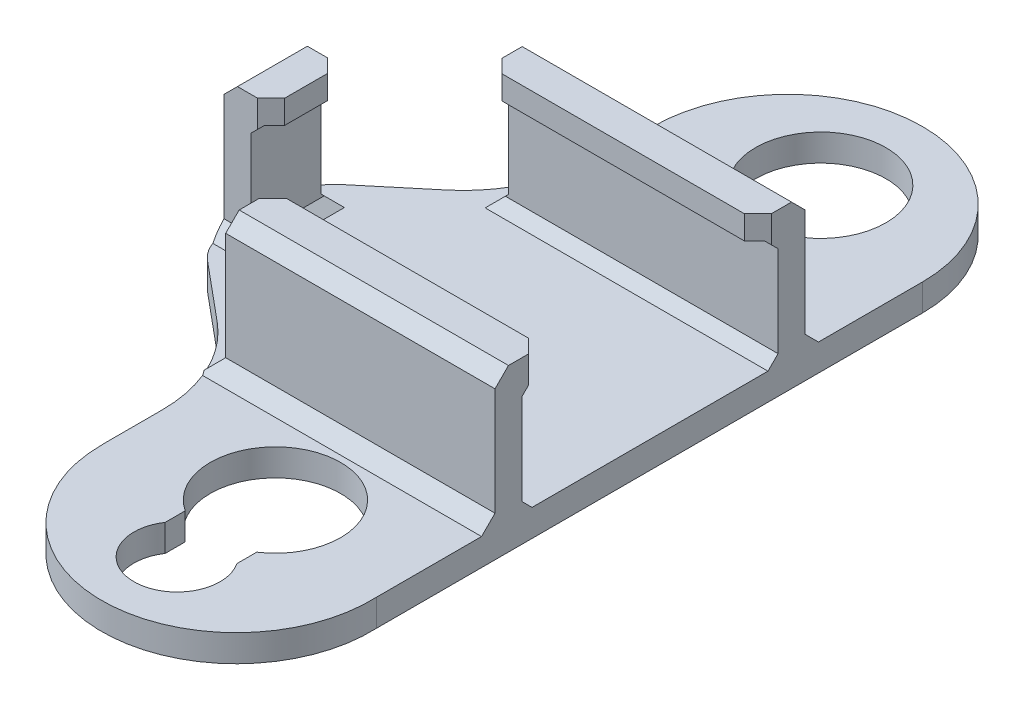
SolidWorks part; units mm, degrees
ref_plane "Front Plane" through (0, 0, 0) normal (0, 0, 1) x (1, 0, 0)
ref_plane "Top Plane" through (0, 0, 0) normal (0, 1, 0) x (1, 0, 0)
ref_plane "Right Plane" through (0, 0, 0) normal (1, 0, 0) x (0, 0, -1)
sketch "Sketch1" plane through (0, 0, 0) normal (0, 1, 0) x (1, 0, 0)
  line L0 (1.6716, 17.1781) -> (1.6716, -5.8219) construction
  line L1 (-8.3284, -14.595) -> (-8.3197, -15.0114)
  line L2 (1.6716, -19.4069) -> (1.6716, -12.0976)
  line L3 (11.6716, -5.8219) -> (-8.3284, -5.8219) construction
  line L4 (11.6716, 17.1781) -> (11.6716, -5.8219)
  line L5 (-17.3284, 8.273) -> (-17.3284, 3.0832)
  line L6 (-11.9265, 14.1796) -> (-16.2489, 10.5776)
  line L7 (-16.2489, 0.7785) -> (-11.9265, -2.8235)
  line L8 (1.6716, 5.6781) -> (-25.0675, 5.6781) construction
  line L9 (4.3293, -17.6245) -> (4.3293, -16.1442)
  line L10 (-0.9861, -17.6245) -> (-0.9861, -16.1442)
  line L11 (4.3293, 22.8677) -> (4.3293, 24.3481)
  line L12 (-0.9861, 22.8677) -> (-0.9861, 24.3481)
  line L13 (1.6716, 21.9934) -> (1.6716, 29.3026)
  line L14 (-8.3284, 25.9512) -> (-8.3284, 21.8618)
  line L15 (11.6716, 25.9512) -> (11.6716, 17.1781)
  line L16 (11.6716, -14.595) -> (11.6716, -5.8219)
  line L17 (-8.3284, -14.595) -> (-8.3284, -10.5057)
  line L18 (11.6716, 17.1781) -> (-8.3284, 17.1781) construction
  arc A0 (-0.9861, -17.6245) -> (4.3293, -17.6245) centre (1.6716, -19.4069) ccw
  arc A1 (4.3293, -16.1442) -> (-0.9861, -16.1442) centre (1.6716, -12.0976) ccw
  arc A2 (4.3293, 24.3481) -> (-0.9861, 24.3481) centre (1.6716, 28.3947) ccw
  arc A3 (-0.9861, 22.8677) -> (4.3293, 22.8677) centre (1.6716, 21.0854) ccw
  arc A4 (11.6716, 25.9512) -> (-8.3284, 25.9512) centre (1.6716, 25.9512) ccw
  arc A5 (-8.3197, -15.0114) -> (11.6716, -14.595) centre (1.6803, -15.0114) ccw
  arc A6 (-8.3284, -10.5057) -> (-11.9265, -2.8235) centre (-18.3284, -10.5057) ccw
  arc A7 (-8.3284, 21.8618) -> (-11.9265, 14.1796) centre (-18.3284, 21.8618) cw
  arc A8 (-16.2489, 0.7785) -> (-17.3284, 3.0832) centre (-14.3284, 3.0832) cw
  arc A9 (-16.2489, 10.5776) -> (-17.3284, 8.273) centre (-14.3284, 8.273) ccw
  point P35 (-17.3284, 1.6781)
  point P38 (-17.3284, 9.6781)
  dimension "D1" = 10
  dimension "D2" = 3
  dimension "D3" = 19
  dimension "D4" = 8
extrude "Boss-Extrude3" add sketch "Sketch1" along normal blind 2 contours L6 A9 L5 A8 L7 A6 L17 L1 A5 L16 L4 L15 A4 L14 A7 A1 L9 A0 L10 A3 L12 A2 L11 region at (-0.1787, 0, -5.4072)
sketch "Sketch2" plane through (0, 2, 0) normal (0, 1, 0) x (1, 0, 0)
  line L0 (11.6716, -14.595) -> (11.6716, 25.9512) construction
  line L1 (-17.3284, 8.273) -> (-15.3284, 8.273)
  line L2 (-17.3284, 8.273) -> (-17.3284, 3.0832)
  line L3 (-17.3284, 3.0832) -> (-15.3284, 3.0832)
  line L4 (-15.3284, 8.273) -> (-15.3284, 3.0832)
  line L5 (11.6716, 17.2264) -> (-8.3284, 17.2264)
  line L6 (11.6716, 17.2264) -> (11.6716, 15.2264)
  line L7 (11.6716, 15.2264) -> (-8.3284, 15.2264)
  line L8 (-8.3284, 17.2264) -> (-8.3284, 15.2264)
  line L10 (11.6716, -5.7923) -> (-8.3284, -5.7923)
  line L11 (11.6716, -5.7923) -> (11.6716, -3.7923)
  line L12 (11.6716, -3.7923) -> (-8.3284, -3.7923)
  line L13 (-8.3284, -5.7923) -> (-8.3284, -3.7923)
  dimension "D1" = 2
  dimension "D2" = 2
  dimension "D3" = 2
extrude "Boss-Extrude4" add sketch "Sketch2" along normal blind 10
sketch "Sketch3" plane through (-15.3284, 0, 0) normal (1, 0, 0) x (0, 0, -1)
  line L0 (8.273, 12) -> (8.273, 2) construction
  line L1 (8.273, 12) -> (3.0832, 12)
  line L2 (8.273, 12) -> (8.273, 10.25)
  line L3 (8.273, 10.25) -> (3.0832, 10.25)
  line L4 (3.0832, 12) -> (3.0832, 10.25)
  line L5 (3.0832, 12) -> (8.273, 12) construction
  line L6 (3.0832, 12) -> (3.0832, 2) construction
  dimension "D1" = 1.75
extrude "Boss-Extrude5" add sketch "Sketch3" along normal blind 1.5
sketch "Sketch4" plane through (0, 0, -15.2264) normal (0, 0, 1) x (1, 0, 0)
  line L0 (11.6716, 12) -> (11.6716, 2) construction
  line L1 (-8.3284, 12) -> (11.6716, 12)
  line L2 (-8.3284, 12) -> (-8.3284, 10.25)
  line L3 (-8.3284, 10.25) -> (11.6716, 10.25)
  line L4 (11.6716, 12) -> (11.6716, 10.25)
  dimension "D1" = 1.75
extrude "Boss-Extrude6" add sketch "Sketch4" along normal blind 1.5
sketch "Sketch5" plane through (0, 0, 3.7923) normal (0, 0, -1) x (-1, 0, 0)
  line L0 (-11.6716, 12) -> (-11.6716, 2) construction
  line L1 (8.3284, 12) -> (-11.6716, 12)
  line L2 (8.3284, 12) -> (8.3284, 10.25)
  line L3 (8.3284, 10.25) -> (-11.6716, 10.25)
  line L4 (-11.6716, 12) -> (-11.6716, 10.25)
  dimension "D1" = 1.75
extrude "Boss-Extrude7" add sketch "Sketch5" along normal blind 1.5
chamfer "Chamfer1" distance 0.75 angle 45 6 edges at (-15.3284, 10.25, -5.6781) (1.6716, 10.25, 3.7923) (1.6716, 10.25, -15.2264) (-15.3284, 2, -5.6781) (1.6716, 2, 3.7923) (1.6716, 2, -15.2264)
chamfer "Chamfer2" distance 1 angle 45 15 edges at (11.6716, 11.125, 2.2923) (11.6716, 11.125, -13.7264) (-8.3284, 11.125, -13.7264) (-13.8284, 11.125, -8.273) (-13.8284, 11.125, -3.0832) (-8.3284, 11.125, 2.2923) (1.6716, 12, -17.2264) (1.6716, 12, 5.7923) (-17.3284, 12, -5.6781) (-15.9534, 2, -3.0832) (-15.9534, 2, -8.273) (-8.3284, 2, -15.8514) (1.6716, 2, -17.2264) (-8.3284, 2, 4.4173) (1.6716, 2, 5.7923)
